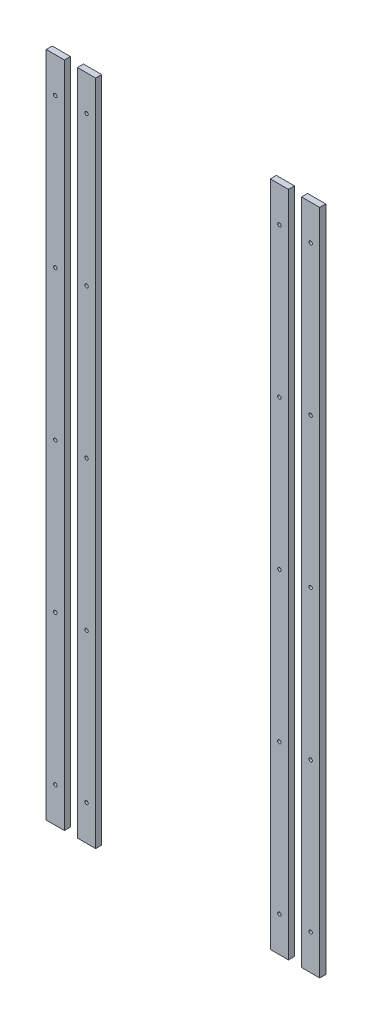
SolidWorks part; units mm, degrees
ref_plane "Спереди" through (0, 0, 0) normal (0, 0, 1) x (1, 0, 0)
ref_plane "Сверху" through (0, 0, 0) normal (0, 1, 0) x (1, 0, 0)
ref_plane "Справа" through (0, 0, 0) normal (1, 0, 0) x (0, 0, -1)
sketch "Четыре_направляющие_эскиз" plane through (0, 0, 0) normal (0, 0, 1) x (1, 0, 0)
  line L0 (315.5, -427) -> (333.5, -427)
  line L1 (333.5, -427) -> (333.5, 235)
  line L2 (333.5, 235) -> (315.5, 235)
  line L3 (315.5, 235) -> (315.5, -427)
  line L4 (346.5, -427) -> (364.5, -427)
  line L5 (364.5, -427) -> (364.5, 235)
  line L6 (364.5, 235) -> (346.5, 235)
  line L7 (346.5, 235) -> (346.5, -427)
  line L8 (537.8, -427) -> (555.8, -427)
  line L9 (555.8, -427) -> (555.8, 235)
  line L10 (555.8, 235) -> (537.8, 235)
  line L11 (537.8, 235) -> (537.8, -427)
  line L12 (568.8, -427) -> (586.8, -427)
  line L13 (586.8, -427) -> (586.8, 235)
  line L14 (586.8, 235) -> (568.8, 235)
  line L15 (568.8, 235) -> (568.8, -427)
  dimension "X001" = 315.5
  dimension "X002" = 333.5
  dimension "X003" = 346.5
  dimension "X004" = 364.5
  dimension "X005" = 537.8
  dimension "X006" = 555.8
  dimension "X007" = 568.8
  dimension "X008" = 586.8
  dimension "Y001" = 427
  dimension "Y002" = 235
extrude "Четыре_направляющие_6мм" add sketch "Четыре_направляющие_эскиз" along normal blind 6
sketch "Крепление_направляющих_М3_эскиз" plane through (0, 0, 0) normal (0, 0, 1) x (1, 0, 0)
  circle A0 centre (324.5, -392) radius 1.7
  circle A1 centre (355.5, -392) radius 1.7
  circle A2 centre (546.8, -392) radius 1.7
  circle A3 centre (577.8, -392) radius 1.7
  dimension "Диаметр001" = 3.4
  dimension "Диаметр002" = 3.4
  dimension "Диаметр003" = 3.4
  dimension "Диаметр004" = 3.4
  dimension "X001" = 324.5
  dimension "X002" = 355.5
  dimension "X003" = 546.8
  dimension "X004" = 577.8
  dimension "Y001" = 392
extrude "Проходы_направляющих_М3" cut sketch "Крепление_направляющих_М3_эскиз" against normal through all and the other way through all
pattern_linear "Массив_крепления_направляющих_5рядов" count 5 spacing 148 along (0, 1, 0) of "Проходы_направляющих_М3"
equation "\"Толщина стенки\" = \"Толщина тонких панелей\""
equation "\"Ширина груза\"= 160"
equation "\"Глубина груза\"= 240"
equation "\"Высота груза\"= 160"
equation "\"Ширина ячейки\"= \"Ширина груза\" + 10"
equation "\"Глубина ячейки\"= \"Глубина груза\" + 10"
equation "\"Высота ячейки\"= \"Высота груза\" + 10 + 13"
equation "\"Колво ячеек ширина\"= 2"
equation "\"Колво ячеек высота\"= 2"
equation "\"Крепление дверцы\"= 5 "
equation "\"Ширина рейки\"= \"Толщина шестерни\""
equation "\"Высота рейки\"= 20"
equation "\"Высота пола\" = 2*\"Толщина тонких панелей\""
equation "\"Колво полозьев\"= 5"
equation "\"Отступ рейки\"= 20"
equation "\"Глубина каретки\"= \"Глубина ячейки\" + 30 + \"Мотор Y высота корпуса\" + 20"
equation "\"Длинна рейки\" = (\"Ширина ячейки\"+\"Толщина вертикальных стенок\"+\"Крепление дверцы\")*\"Колво ячеек ширина\"+\"Ширина ячейки выгрузки\"*\"Колво выгрузки\"+\"Толщина вертикальных стенок\"+2*\"Отступ крепления мотора фиксации\"-\"Крепление дверцы\"*\"Колво ячеек ширина\""
equation "\"Отступ шпильки\"= 26"
equation "\"Диаметр шпильки\"= 5"
equation "\"Длинна шпильки\" = (\"Высота ячейки\"+\"Толщина горизонтальных плит\"+\"Высота пола\")*\"Колво ячеек высота\"+2*(\"Толщина горизонтальных плит\"+\"Отступ рейки\")"
equation "\"Ширина пластины\"= 50  "
equation "\"Высота зона выгрузки\"= \"Высота ячейки\" * 2 + \"Толщина стенки\" * 2"
equation "\"Колво выгрузки\"= 1"
equation "\"Ширина ячейки выгрузки\" = \"Ширина ячейки\"+\"Толщина вертикальных стенок\"+2*\"Отступ крепления мотора фиксации\""
equation "\"Отступ крепления мотора фиксации\" = (\"Ширина пластины\"+20-\"Толщина вертикальных стенок\")/2"
equation "\"Мотор X ширина корпуса\"= 42.3"
equation "\"Мотор X высота корпуса\"= 42.3"
equation "\"Мотор X длина корпуса\"= 40"
equation "\"Мотор X вылет вала\"= 19.8"
equation "\"Мотор Y ширина корпуса\"= 42.3"
equation "\"Мотор Y высота корпуса\"= 42.3"
equation "\"Мотор Y длина корпуса\"= 48"
equation "\"Мотор Y вылет вала\"= 30"
equation "\"Мотор Z ширина корпуса\"= 42"
equation "\"Мотор Z высота корпуса\"= 42"
equation "\"Мотор Z длина корпуса\"= 40"
equation "\"Мотор Z вылет вала\"= 23"
equation "\"Мотор диаметр вала ПРЕДВ\"= 5"
equation "\"Мотор шаг крепления ПРЕДВ\"= 31"
equation "\"Мотор диаметр отверстий ПРЕДВ\"= 3"
equation "\"Мотор глубина отверстий ПРЕДВ\"= 4.5"
equation "\"Мотор диаметр буртика ПРЕДВ\"= 22"
equation "\"Мотор высота буртика ПРЕДВ\"= 2"
equation "\"Мотор диаметр шкива ПРЕДВ\"= 16"
equation "\"Мотор длина шкива ПРЕДВ\"= 12"
equation "\"Мотор отступ шкива ПРЕДВ\"= 5"
equation "\"Мотор X шаг градусов\"= 1.8"
equation "\"Мотор Y шаг градусов\"= 1.8"
equation "\"Мотор Z шаг градусов\"= 1.8"
equation "\"Мотор Y диаметр ротора\"= 25.78"
equation "\"Толщина шестерни\"= 10"
equation "\"Толщина тонких панелей\" = 6"
equation "\"Толщина вертикальных стенок\" = 6"
equation "\"Толщина горизонтальных плит\" = 6"
equation "\"Базовая высота корпуса\"= (\"Высота ячейки\"+\"Толщина тонких панелей\"+\"Высота пола\")*\"Колво ячеек высота\"+6*\"Толщина тонких панелей\"+\"Мотор X ширина корпуса\"+\"Мотор Y ширина корпуса\"+75"
equation "\"Высота корпуса\"= (\"Высота ячейки\"+\"Толщина горизонтальных плит\"+\"Высота пола\")*\"Колво ячеек высота\"+2*\"Толщина горизонтальных плит\"+4*\"Толщина тонких панелей\"+\"Мотор X ширина корпуса\"+\"Мотор Y ширина корпуса\"+75"
equation "\"Смещение центра корпуса\"= (\"Высота корпуса\"-\"Базовая высота корпуса\")/2-(\"Толщина горизонтальных плит\"-\"Толщина тонких панелей\")"
equation "\"Отметка пола\"= -\"Базовая высота корпуса\"/2+\"Толщина тонких панелей\""
equation "\"Отметка потолка\"= \"Отметка пола\"+\"Высота корпуса\"-2*\"Толщина горизонтальных плит\""
equation "\"Отметка верхней полки\"= \"Отметка потолка\"-(28+\"Толщина тонких панелей\")-\"Высота ячейки\"-\"Высота пола\""
equation "\"Отметка нижней полки\"= \"Отметка верхней полки\"-\"Высота ячейки\"-\"Высота пола\"-\"Толщина горизонтальных плит\""
equation "\"Ширина направляющей\"= 18"
equation "\"X001@Четыре_направляющие_эскиз\" = (\"Глубина ячейки\"+74.5-9)"
equation "\"X002@Четыре_направляющие_эскиз\" = (\"Глубина ячейки\"+74.5+9)"
equation "\"X003@Четыре_направляющие_эскиз\" = (\"Глубина ячейки\"+105.5-9)"
equation "\"X004@Четыре_направляющие_эскиз\" = (\"Глубина ячейки\"+105.5+9)"
equation "\"X005@Четыре_направляющие_эскиз\" = (2*\"Глубина ячейки\"+46.8-9)"
equation "\"X006@Четыре_направляющие_эскиз\" = (2*\"Глубина ячейки\"+46.8+9)"
equation "\"X007@Четыре_направляющие_эскиз\" = (2*\"Глубина ячейки\"+77.8-9)"
equation "\"X008@Четыре_направляющие_эскиз\" = (2*\"Глубина ячейки\"+77.8+9)"
equation "\"Y001@Четыре_направляющие_эскиз\" = -(-(2*\"Ширина ячейки\"+87))"
equation "\"Y002@Четыре_направляющие_эскиз\" = (\"Ширина ячейки\"+65)"
equation "\"D1@Четыре_направляющие_6мм\" = \"Толщина тонких панелей\""
equation "\"X001@Крепление_направляющих_М3_эскиз\" = (\"Глубина ячейки\"+74.5)"
equation "\"X002@Крепление_направляющих_М3_эскиз\" = (\"Глубина ячейки\"+105.5)"
equation "\"X003@Крепление_направляющих_М3_эскиз\" = (2*\"Глубина ячейки\"+46.8)"
equation "\"X004@Крепление_направляющих_М3_эскиз\" = (2*\"Глубина ячейки\"+77.8)"
equation "\"Y001@Крепление_направляющих_М3_эскиз\" = -(-(2*\"Ширина ячейки\"+87)+35)"
equation "\"Диаметр001@Крепление_направляющих_М3_эскиз\" = 3.4"
equation "\"Диаметр002@Крепление_направляющих_М3_эскиз\" = 3.4"
equation "\"Диаметр003@Крепление_направляющих_М3_эскиз\" = 3.4"
equation "\"Диаметр004@Крепление_направляющих_М3_эскиз\" = 3.4"
equation "\"D3@Массив_крепления_направляющих_5рядов\" = (\"Длинна рейки\"-70)/4"
